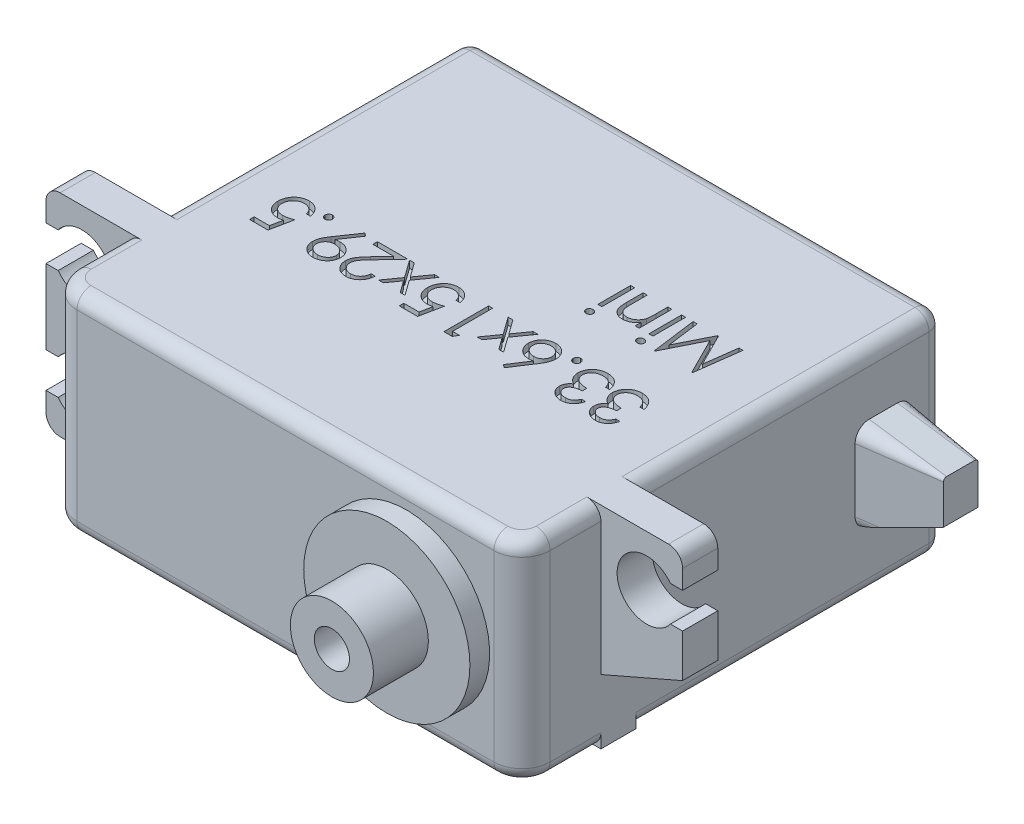
SolidWorks part; units mm, degrees
ref_plane "Front" through (0, 0, 0) normal (0, 0, 1) x (1, 0, 0)
ref_plane "Top" through (0, 0, 0) normal (0, 1, 0) x (1, 0, 0)
ref_plane "Right" through (0, 0, 0) normal (1, 0, 0) x (0, 0, -1)
sketch "Sketch1" plane through (0, 0, 0) normal (0, 0, 1) x (1, 0, 0)
  line L1 (-16.8, -7.5) -> (16.8, -7.5)
  line L2 (-16.8, -7.5) -> (-16.8, 7.5)
  line L3 (-16.8, 7.5) -> (16.8, 7.5)
  line L4 (16.8, -7.5) -> (16.8, 7.5)
  line L5 (-16.8, -7.5) -> (16.8, 7.5) construction
  line L6 (-16.8, 7.5) -> (16.8, -7.5) construction
  point P0 (0, 0)
  dimension "D1" = 15
  dimension "D2" = 33.6
extrude "Boss-Extrude1" add sketch "Sketch1" along normal mid plane 29.9
sketch "Sketch2" plane through (0, 0, 0) normal (0, 1, 0) x (1, 0, 0)
  line L1 (-22.6, -9.35) -> (22.6, -9.35)
  line L2 (-22.6, -9.35) -> (-22.6, -6.85)
  line L3 (-22.6, -6.85) -> (22.6, -6.85)
  line L4 (22.6, -9.35) -> (22.6, -6.85)
  line L5 (-22.6, -9.35) -> (22.6, -6.85) construction
  line L6 (-22.6, -6.85) -> (22.6, -9.35) construction
  line L8 (16.8, 14.95) -> (-16.8, 14.95) construction
  point P0 (0, -8.1)
  dimension "D1" = 2.5
  dimension "D2" = 45.2
  dimension "D3" = 21.8
extrude "Boss-Extrude2" add sketch "Sketch2" along normal up to vertex (7.5 mm away) and the other way up to vertex (7.5 mm away) up to point (-16.8, 7.5, 14.95) other way up to point (-16.8, -7.5, -14.95)
sketch "Sketch6" plane through (0, 0, 9.35) normal (0, 0, 1) x (1, 0, 0)
  line L0 (0, 7.5) -> (0, -7.5) construction
  line L1 (16.8, 7.5) -> (-16.8, 7.5) construction
  line L2 (-16.8, -7.5) -> (16.8, -7.5) construction
  line L3 (-22.6, 5.15) -> (-21.7375, 5.15)
  line L4 (22.6, 7.5) -> (22.6, -7.5) construction
  line L5 (22.6, 0) -> (-22.6, 0) construction
  line L6 (-22.6, 7.5) -> (-22.6, -7.5) construction
  line L7 (-22.6, 2.65) -> (-21.7375, 2.65)
  line L8 (-20.05, 3.9) -> (-21.6411, 3.9) construction
  line L9 (-22.6, 5.15) -> (-22.6, 2.65)
  line L10 (22.6, 2.65) -> (21.7375, 2.65)
  line L11 (22.6, 5.15) -> (22.6, 2.65)
  line L12 (22.6, 5.15) -> (21.7375, 5.15)
  line L13 (22.6, -2.65) -> (21.7375, -2.65)
  line L14 (22.6, -5.15) -> (22.6, -2.65)
  line L15 (22.6, -5.15) -> (21.7375, -5.15)
  line L16 (-22.6, -2.65) -> (-21.7375, -2.65)
  line L17 (-22.6, -5.15) -> (-22.6, -2.65)
  line L18 (-22.6, -5.15) -> (-21.7375, -5.15)
  arc A0 (-21.7375, 2.65) -> (-21.7375, 5.15) centre (-20.05, 3.9) ccw
  arc A1 (21.7375, 2.65) -> (21.7375, 5.15) centre (20.05, 3.9) cw
  arc A2 (21.7375, -2.65) -> (21.7375, -5.15) centre (20.05, -3.9) ccw
  arc A3 (-21.7375, -2.65) -> (-21.7375, -5.15) centre (-20.05, -3.9) cw
  dimension "D3" = 4.2
  dimension "D1" = 40.1
  dimension "D2" = 7.8
  dimension "D4" = 2.5
extrude "Cut-Extrude2" cut sketch "Sketch6" against normal blind 10
sketch "Sketch3" plane through (0, 0, 14.95) normal (0, 0, 1) x (1, 0, 0)
  line L0 (22.6, 2.65) -> (22.6, -2.65) construction
  circle A0 centre (8.6, 0) radius 2.95
  dimension "D2" = 5.9
  dimension "D1" = 14
extrude "Boss-Extrude3" add sketch "Sketch3" along normal blind 5.3
sketch "Sketch4" plane through (0, 7.5, 0) normal (0, -1, 0) x (1, 0, 0)
  text T0 "33.6x15x29.5\r\nMini" font "Century Gothic" height in points 12
extrude "Cut-Extrude1" cut sketch "Sketch4" along normal blind 0.5
sketch "Sketch5" [suppressed] plane through (0, 0, 16.95) normal (0, 0, 1) x (1, 0, 0)
  circle A0 centre (10.5356, 0) radius 10
  dimension "D1" = 20
ref_axis "Axis1" [suppressed] through (10.5356, 0, 16.95) along (0, 0, -1)
sketch "Sketch7" plane through (0, 0, 14.95) normal (0, 0, 1) x (1, 0, 0)
  circle A0 centre (8.6, 0) radius 5.9
  dimension "D1" = 11.8
extrude "Boss-Extrude4" add sketch "Sketch7" along normal blind 1.4
fillet "Fillet1" radius 2 2 edges at (-16.8, 0, 14.95) (16.8, 0, 14.95)
sketch "Sketch8" plane through (16.8, 0, 0) normal (1, 0, 0) x (0, 0, -1)
  line L0 (14.95, -7.5) -> (14.95, 7.5) construction
  line L1 (9.7, 3.25) -> (11.7, 3.25)
  line L2 (8.7, 2.25) -> (8.7, -2.25)
  line L3 (9.7, -3.25) -> (11.7, -3.25)
  line L4 (12.7, 2.25) -> (12.7, -2.25)
  arc A0 (11.7, -3.25) -> (12.7, -2.25) centre (11.7, -2.25) ccw
  arc A1 (8.7, -2.25) -> (9.7, -3.25) centre (9.7, -2.25) ccw
  arc A2 (9.7, 3.25) -> (8.7, 2.25) centre (9.7, 2.25) ccw
  arc A3 (11.7, 3.25) -> (12.7, 2.25) centre (11.7, 2.25) cw
  point P4 (8.7, 0)
  point P10 (12.7, -3.25)
  point P15 (8.7, 3.25)
  point P18 (12.7, 3.25)
  dimension "D4" = 1
  dimension "D5" = 1
  dimension "D1" = 4
  dimension "D2" = 6.5
  dimension "D3" = 2.25
extrude "Boss-Extrude5" add sketch "Sketch8" along normal blind 5.5 draft 8
sketch "Sketch10" plane through (0, -7.5, 0) normal (0, -1, 0) x (1, 0, 0)
  line L12 (14.8, 14.95) -> (-14.8, 14.95)
  line L13 (-16.8, 12.95) -> (-16.8, 9.35)
  line L14 (-16.8, 9.35) -> (-22.6, 9.35)
  line L15 (-22.6, 9.35) -> (-22.6, 6.85)
  line L16 (-22.6, 6.85) -> (-16.8, 6.85)
  line L17 (-16.8, 6.85) -> (-16.8, -14.95)
  line L18 (-16.8, -14.95) -> (16.8, -14.95)
  line L19 (16.8, -14.95) -> (16.8, 6.85)
  line L20 (16.8, 6.85) -> (22.6, 6.85)
  line L21 (22.6, 6.85) -> (22.6, 9.35)
  line L22 (22.6, 9.35) -> (16.8, 9.35)
  line L23 (16.8, 9.35) -> (16.8, 12.95)
  line L24 (14.8, 14.95) -> (-14.8, 14.95)
  line L25 (-16.8, 12.95) -> (-16.8, 9.35)
  line L26 (-16.8, 9.35) -> (-22.6, 9.35)
  line L27 (-22.6, 9.35) -> (-22.6, 6.85)
  line L28 (-22.6, 6.85) -> (-16.8, 6.85)
  line L29 (-16.8, 6.85) -> (-16.8, -14.95)
  line L30 (-16.8, -14.95) -> (16.8, -14.95)
  line L31 (16.8, -14.95) -> (16.8, 6.85)
  line L32 (16.8, 6.85) -> (22.6, 6.85)
  line L33 (22.6, 6.85) -> (22.6, 9.35)
  line L34 (22.6, 9.35) -> (16.8, 9.35)
  line L35 (16.8, 9.35) -> (16.8, 12.95)
  arc A2 (-14.8, 14.95) -> (-16.8, 12.95) centre (-14.8, 12.95) ccw
  arc A3 (16.8, 12.95) -> (14.8, 14.95) centre (14.8, 12.95) ccw
  arc A4 (-14.8, 14.95) -> (-16.8, 12.95) centre (-14.8, 12.95) ccw
  arc A5 (16.8, 12.95) -> (14.8, 14.95) centre (14.8, 12.95) ccw
  dimension "D1" = 0
fillet "Fillet2" radius 1 18 edges at (-16.8, -7.5, 11.15) (-16.2142, -7.5, 14.3642) (16.8, -7.5, 11.15) (16.2142, -7.5, 14.3642) (-16.8, 7.5, 11.15) (-16.2142, 7.5, 14.3642) (0, 7.5, 14.95) (16.2142, 7.5, 14.3642) (0, -7.5, 14.95) (16.8, 7.5, 11.15) (16.8, 7.5, -4.05) (16.8, 0, -14.95) (0, 7.5, -14.95) (-16.8, 7.5, -4.05) (-16.8, 0, -14.95) (0, -7.5, -14.95) (-16.8, -7.5, -4.05) (16.8, -7.5, -4.05)
fillet "Fillet3" radius 1 4 edges at (22.6, 7.5, 8.1) (-22.6, 7.5, 8.1) (22.6, -7.5, 8.1) (-22.6, -7.5, 8.1)
sketch "Sketch9" plane through (0, 0, 20.25) normal (0, 0, 1) x (1, 0, 0)
  circle A0 centre (8.6, 0) radius 1.25
  dimension "D1" = 2.5
extrude "Cut-Extrude3" cut sketch "Sketch9" against normal blind 3
sketch "Sketch11" plane through (0, 0, 9.35) normal (0, 0, 1) x (1, 0, 0)
  line L0 (22.6, -0.6147) -> (16.8, 1.8091)
  line L10 (22.6, 5.15) -> (22.6, 6.5)
  line L11 (21.6, 7.5) -> (15.8, 7.5)
  line L12 (16.8, 6.5) -> (16.8, -6.5)
  line L13 (15.8, -7.5) -> (21.6, -7.5)
  line L14 (22.6, -6.5) -> (22.6, -5.15)
  line L15 (22.6, -5.15) -> (21.7375, -5.15)
  line L16 (21.7375, -2.65) -> (22.6, -2.65)
  line L17 (22.6, -2.65) -> (22.6, 2.65)
  line L18 (22.6, 2.65) -> (21.7375, 2.65)
  line L19 (21.7375, 5.15) -> (22.6, 5.15)
  line L20 (22.6, 5.15) -> (22.6, 6.5)
  line L21 (21.6, 7.5) -> (15.8, 7.5)
  line L22 (16.8, 6.5) -> (16.8, 1.8091)
  line L27 (22.6, -0.6147) -> (22.6, 2.65)
  line L28 (22.6, 2.65) -> (21.7375, 2.65)
  line L29 (21.7375, 5.15) -> (22.6, 5.15)
  arc A6 (22.6, 6.5) -> (21.6, 7.5) centre (21.6, 6.5) ccw
  arc A7 (16.8, 6.5) -> (15.8, 7.5) centre (15.8, 6.5) ccw
  arc A8 (15.8, -7.5) -> (16.8, -6.5) centre (15.8, -6.5) ccw
  arc A9 (21.6, -7.5) -> (22.6, -6.5) centre (21.6, -6.5) ccw
  arc A10 (21.7375, -2.65) -> (21.7375, -5.15) centre (20.05, -3.9) ccw
  arc A11 (21.7375, 5.15) -> (21.7375, 2.65) centre (20.05, 3.9) ccw
  arc A12 (22.6, 6.5) -> (21.6, 7.5) centre (21.6, 6.5) ccw
  arc A13 (16.8, 6.5) -> (15.8, 7.5) centre (15.8, 6.5) ccw
  arc A17 (21.7375, 5.15) -> (21.7375, 2.65) centre (20.05, 3.9) ccw
  dimension "D1" = 0
extrude "Cut-Extrude4" [suppressed] cut sketch "Sketch11" against normal blind 3
sketch "Sketch12" plane through (0, 0, 9.35) normal (0, 0, 1) x (1, 0, 0)
  line L0 (22.6, -0.3976) -> (16.8, -2.9223)
  line L1 (22.6, 2.65) -> (22.6, -2.65) construction
  line L2 (16.8, 6.5) -> (16.8, -6.5) construction
  line L3 (16.8, -2.9223) -> (16.8, -8.775)
  line L4 (16.8, -8.775) -> (22.6, -8.775)
  line L5 (22.6, -8.775) -> (22.6, -0.3976)
extrude "Cut-Extrude5" cut sketch "Sketch12" against normal through all
